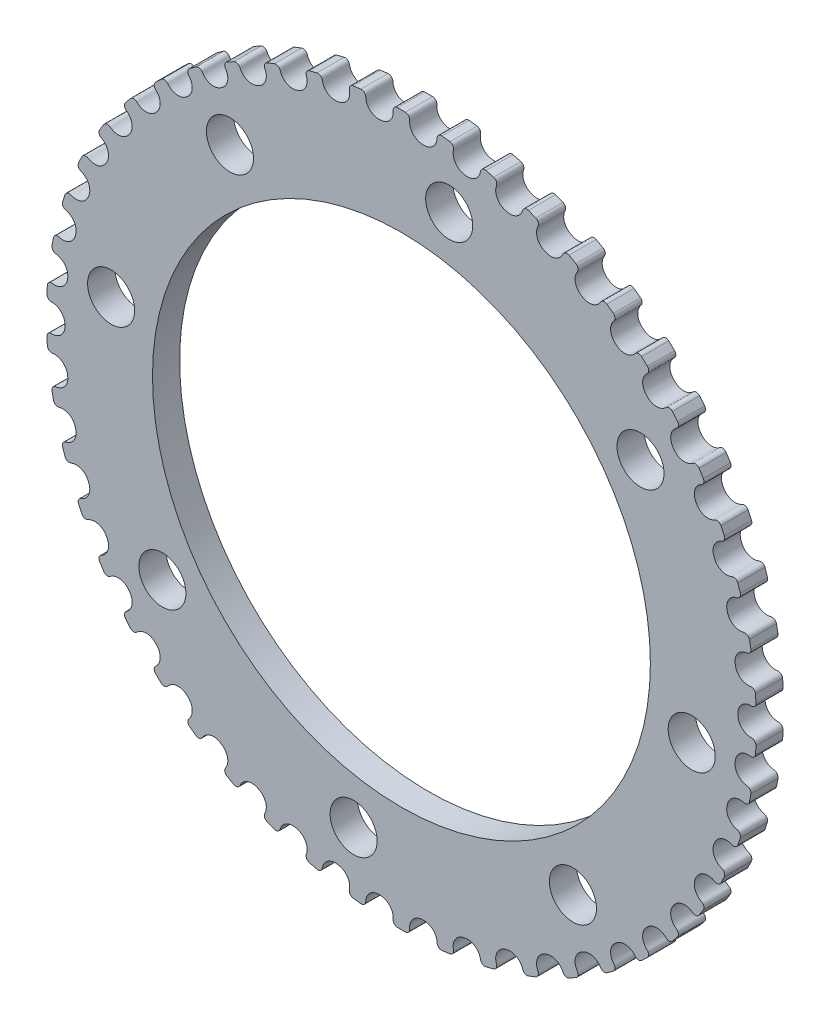
SolidWorks part; units mm, degrees
material "Thornel Mat VMA"
ref_plane "Front Plane" through (0, 0, 0) normal (0, 0, 1) x (1, 0, 0)
ref_plane "Top Plane" through (0, 0, 0) normal (0, 1, 0) x (1, 0, 0)
ref_plane "Right Plane" through (0, 0, 0) normal (1, 0, 0) x (0, 0, -1)
ref_axis "Axis1" through (0, 0, 55) along (0, 0, -1)
sketch "SketchRevolveGearBelt01" plane through (0, 0, 0) normal (1, 0, 0) x (0, 0, -1)
  line L0 (0, 0) -> (1, 0) construction
  line L1 (1.5, 0) -> (1.5, 39.2172)
  line L2 (1.5, 39.2172) -> (-1.5, 39.2172)
  line L3 (-1.5, 39.2172) -> (-1.5, 0)
  line L4 (-1.5, 0) -> (1.5, 0)
  dimension "GearBeltSide1" = 1.5
  dimension "GearBeltOutsideDiameter" = 39.2172
  dimension "GearBeltSide2" = 1.5
revolve "GearBelt01" add sketch "SketchRevolveGearBelt01" angle 360 about L0
sketch "SketchToothGearBelt01" plane through (0, 0, 0) normal (0, 0, 1) x (1, 0, 0)
  arc A0 (39.1647, 2.0323) -> (39.1647, -2.0323) centre (0, 0) cw
  spline S0 degree 3 poles (39.1647, -2.0323) (39.166, -2.006) (39.1649, -1.9663) (39.1569, -1.9141) (39.1478, -1.8755) (39.1356, -1.8378) (39.1204, -1.8013) (39.1023, -1.7661) (39.0814, -1.7324) (39.0578, -1.7006) (39.0317, -1.6708) (39.0033, -1.6432) (38.9728, -1.618) (38.9403, -1.5953) (38.9061, -1.5754) (38.8703, -1.5582) (38.8333, -1.5441) (38.7953, -1.533) (38.7565, -1.525) (38.7172, -1.5201) (38.6658, -1.5185) (38.59, -1.5198) (38.4897, -1.516) (38.3775, -1.5026) (38.2667, -1.4805) (38.158, -1.4498) (38.052, -1.4107) (37.9494, -1.3633) (37.8509, -1.3081) (37.7569, -1.2453) (37.6682, -1.1753) (37.5853, -1.0986) (37.5086, -1.0156) (37.4387, -0.9268) (37.376, -0.8329) (37.3208, -0.7343) (37.2735, -0.6317) (37.2344, -0.5257) (37.2037, -0.4169) (37.1817, -0.3061) (37.1683, -0.1939) (37.1652, -0.1051) (37.1655, -0.0405) (37.1655, 0) (37.1655, 0.0405) (37.1652, 0.1051) (37.1683, 0.1939) (37.1817, 0.3061) (37.2037, 0.4169) (37.2344, 0.5257) (37.2735, 0.6317) (37.3208, 0.7343) (37.376, 0.8329) (37.4387, 0.9268) (37.5086, 1.0156) (37.5853, 1.0986) (37.6682, 1.1753) (37.7569, 1.2453) (37.8509, 1.3081) (37.9494, 1.3633) (38.052, 1.4107) (38.158, 1.4498) (38.2667, 1.4805) (38.3775, 1.5026) (38.4897, 1.516) (38.59, 1.5198) (38.6658, 1.5185) (38.7172, 1.5201) (38.7565, 1.525) (38.7953, 1.533) (38.8333, 1.5441) (38.8703, 1.5582) (38.9061, 1.5754) (38.9403, 1.5953) (38.9728, 1.618) (39.0033, 1.6432) (39.0317, 1.6708) (39.0578, 1.7006) (39.0814, 1.7324) (39.1023, 1.7661) (39.1204, 1.8013) (39.1356, 1.8378) (39.1478, 1.8755) (39.1569, 1.9141) (39.1649, 1.9663) (39.166, 2.006) (39.1647, 2.0323) knots 0 0 0 0 0.012346 0.01852 0.024693 0.030866 0.037039 0.043212 0.049386 0.055559 0.061732 0.067905 0.074078 0.080252 0.086425 0.092598 0.098771 0.104944 0.111118 0.117291 0.123464 0.135171 0.152781 0.17039 0.188 0.205609 0.223219 0.240828 0.258438 0.276048 0.293657 0.311267 0.328876 0.346486 0.364095 0.381705 0.399315 0.416924 0.434534 0.452143 0.469753 0.487362 0.493681 0.5 0.506319 0.512638 0.530247 0.547857 0.565466 0.583076 0.600685 0.618295 0.635905 0.653514 0.671124 0.688733 0.706343 0.723952 0.741562 0.759172 0.776781 0.794391 0.812 0.82961 0.847219 0.864829 0.876536 0.882709 0.888882 0.895056 0.901229 0.907402 0.913575 0.919748 0.925922 0.932095 0.938268 0.944441 0.950614 0.956788 0.962961 0.969134 0.975307 0.98148 0.987654 1 1 1 1
extrude "ToothExtrudeCutGearBelt01" cut sketch "SketchToothGearBelt01" against normal blind 7.239 and the other way blind 7.239
pattern_circular "PatternGearBelt01" count 50 every 7.2 about axis through (0, 0, 55) along (0, 0, -1) of "ToothExtrudeCutGearBelt01"
sketch "BoreRevolveSketch" plane through (0, 0, 0) normal (1, 0, 0) x (0, 0, -1)
  line L0 (0, 0) -> (1, 0) construction
  line L1 (-7.239, 0) -> (7.239, 0)
  line L2 (7.239, 0) -> (7.239, 27.5)
  line L3 (7.239, 27.5) -> (-7.239, 27.5)
  line L4 (-7.239, 27.5) -> (-7.239, 0)
  dimension "BoreSide1" = 7.239
  dimension "TaperSide1" = 27.5
  dimension "BoreSide2" = 7.239
  dimension "TaperSide2" = 27.5
revolve "BoreRevolveCut" cut sketch "BoreRevolveSketch" angle 360 about L0
sketch "AuxiliarySketchGearBelt01" plane through (0, 0, 0) normal (0, 0, 1) x (1, 0, 0)
  circle A0 centre (0, 0) radius 39.7887 construction
  dimension "PitchDiameter" = 79.5774
sketch "Sketch1" plane through (0, 0, 1.5) normal (0, 0, 1) x (1, 0, 0)
  circle A0 centre (-26.4084, -18.9432) radius 2 construction
  circle A1 centre (-5.2787, -32.0684) radius 2 construction
  circle A2 centre (18.9432, -26.4084) radius 2 construction
  circle A3 centre (32.0684, -5.2787) radius 2 construction
  circle A4 centre (26.4084, 18.9432) radius 2 construction
  circle A5 centre (5.2787, 32.0684) radius 2 construction
  circle A6 centre (-18.9432, 26.4084) radius 2 construction
  circle A7 centre (-32.0684, 5.2787) radius 2 construction
  circle A8 centre (-26.4084, -18.9432) radius 2 construction
  circle A9 centre (-5.2787, -32.0684) radius 2 construction
  circle A10 centre (18.9432, -26.4084) radius 2 construction
  circle A11 centre (32.0684, -5.2787) radius 2 construction
  circle A12 centre (26.4084, 18.9432) radius 2 construction
  circle A13 centre (5.2787, 32.0684) radius 2 construction
  circle A14 centre (-18.9432, 26.4084) radius 2 construction
  circle A15 centre (-32.0684, 5.2787) radius 2 construction
  circle A16 centre (-18.9432, 26.4084) radius 2.6
  circle A17 centre (5.2787, 32.0684) radius 2.6
  circle A18 centre (26.4084, 18.9432) radius 2.6
  circle A19 centre (-32.0684, 5.2787) radius 2.6
  circle A20 centre (-26.4084, -18.9432) radius 2.6
  circle A21 centre (-5.2787, -32.0684) radius 2.6
  circle A22 centre (18.9432, -26.4084) radius 2.6
  circle A23 centre (32.0684, -5.2787) radius 2.6
  dimension "D1" = 5.2
extrude "Cut-Extrude1" cut sketch "Sketch1" against normal blind 10
